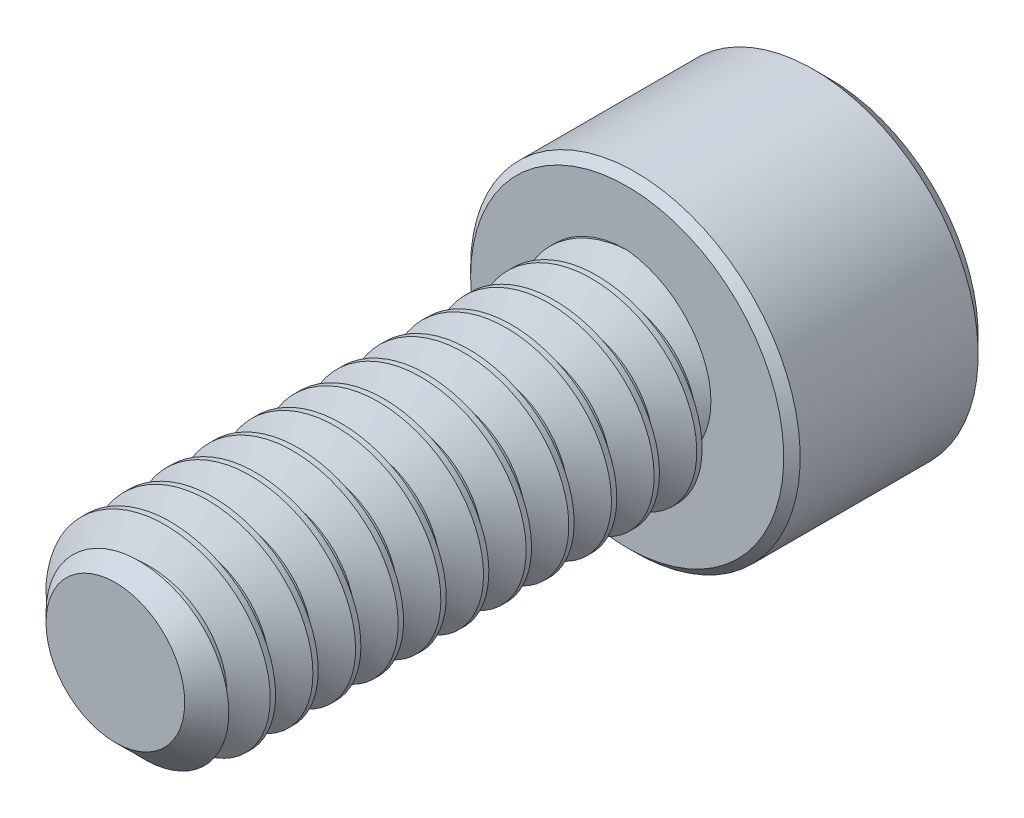
SolidWorks part; units mm, degrees
ref_plane "Front Plane" through (0, 0, 0) normal (0, 0, 1) x (1, 0, 0)
ref_plane "Top Plane" through (0, 0, 0) normal (0, 1, 0) x (1, 0, 0)
ref_plane "Right Plane" through (0, 0, 0) normal (1, 0, 0) x (0, 0, -1)
sketch "Sketch0" plane through (0, 0, 0) normal (1, 0, 0) x (0, 0, -1)
  line L0 (0, 0) -> (6.35, 0) construction
  point P2 (8.8646, 0)
  point P4 (0, 0)
  dimension "D1" = 6.35
  dimension "D2" = 2.5146
  dimension "Min Thread" = 0
sketch "Sketch1" plane through (0, 0, 0) normal (0, 0, 1) x (1, 0, 0)
  circle A0 centre (0, 0) radius 1.2573
  dimension "OD" = 2.5146
extrude "Extrude1" add sketch "Sketch1" against normal blind 6.35
sketch "Sketch2" plane through (0, 0, 0) normal (0, 0, 1) x (1, 0, 0)
  circle A0 centre (0, 0) radius 1.2573 construction
  circle A1 centre (0, 0) radius 1.2573
curve "Helix/Spiral1" pitch 0.5292 height 6.8792 radius 1.2573 centre (0, 0, 0) axis (0, 0, -1) start towards (0, 1, 0) parameters "pitch"=0.5292
chamfer "Chamfer3" distance 0.3969 angle 45 1 edges at (1.2573, 0, 0)
sketch "Sketch3" plane through (0, 0, 0) normal (1, 0, 0) x (0, 0, -1)
  line L0 (-0.463, 1.2573) -> (-0.2646, 0.9136)
  line L1 (-0.2646, 0.9136) -> (-0.1984, 0.9136)
  line L2 (-0.1984, 0.9136) -> (0, 1.2573)
  line L3 (-0.463, 1.2573) -> (0, 1.2573)
  line L4 (-0.2315, 1.2573) -> (-0.2315, 0.9136) construction
  line L5 (-0.3638, 1.0854) -> (-0.0992, 1.0854) construction
  line L6 (0, 1.2573) -> (0, -1.2573) construction
  dimension "D1" = 0.0661
  dimension "D2" = 0.2646
  dimension "D3" = 60
sweep "Cut-Sweep1" cut profiles "Sketch3" path "Helix/Spiral1" align with end faces yes
sketch "Sketch5" plane through (0, 0, 0) normal (1, 0, 0) x (0, 0, -1)
  line L0 (6.35, -0.9237) -> (6.35, 0.8971) construction
  line L1 (6.35, 1.2573) -> (0, 1.2573)
  line L2 (6.35, 1.2573) -> (6.35, 0)
  line L3 (6.35, 0) -> (-0.4576, 0)
  line L4 (0, 0) -> (6.35, 0) construction
  line L5 (0, 1.2573) -> (-0.4576, 0)
  line L6 (0, 0) -> (8.89, 0) construction
  dimension "D1" = 70
  dimension "D3" = 2.54
revolve "partially thread" [suppressed] add sketch "Sketch5" angle 360 about L6
sketch "Sketch6" plane through (0, 0, -6.35) normal (0, 0, -1) x (-1, 0, 0)
  circle A0 centre (0, 0) radius 2.0447
  dimension "head dia" = 4.0894
extrude "Extrude2" add sketch "Sketch6" along normal blind 2.5146
sketch "Sketch7" plane through (0, 0, -8.8646) normal (0, 0, -1) x (-1, 0, 0)
  line L1 (0, 1.1457) -> (-0.9922, 0.5728)
  line L2 (-0.9922, 0.5728) -> (-0.9922, -0.5728)
  line L3 (-0.9922, -0.5728) -> (0, -1.1457)
  line L4 (0, -1.1457) -> (0.9922, -0.5728)
  line L5 (0.9922, -0.5728) -> (0.9922, 0.5728)
  line L6 (0.9922, 0.5728) -> (0, 1.1457)
  circle A0 centre (0, 0) radius 0.9922 construction
  dimension "hex dia" = 1.9844
extrude "Cut-Extrude1" cut sketch "Sketch7" against normal blind 1.4883
sketch "Sketch8" plane through (0, 0, -8.8646) normal (0, 0, -1) x (-1, 0, 0)
  circle A0 centre (0, 0) radius 1.1457
extrude "Cut-Extrude2" cut sketch "Sketch8" against normal through all draft 45
chamfer "Chamfer1" distance 0.2045 angle 45 1 edges at (-2.0447, 0, -8.8646)
chamfer "Chamfer2" distance 0.1022 angle 45 1 edges at (-2.0447, 0, -6.35)
sketch "Sketch9" plane through (0, 0, 0) normal (1, 0, 0) x (0, 0, -1)
  line L0 (0, 1.2573) -> (0, -1.2573) construction
  line L1 (1.8521, 1.2573) -> (1.8521, -1.2573) construction
  line L2 (8.8646, 2.0447) -> (8.8646, -2.0447) construction
  line L3 (6.35, 2.0447) -> (6.35, -2.0447) construction
  line L4 (6.35, 1.9425) -> (6.35, -1.9425) construction
  line L5 (8.8646, -1.8402) -> (8.8646, 1.8402) construction
  line L6 (6.35, -2.0447) -> (6.35, 2.0447) construction
  line L7 (0, 0.8604) -> (0, -0.8604) construction
  line L8 (-0.463, 1.2573) -> (0, 1.2573) construction
  line L9 (1.8521, 0) -> (0, 0) construction
  dimension "D1" = 1.8521
equation "\"D3@Helix/Spiral1\" = \"screw length@Extrude1\"+\"pitch@Helix/Spiral1\""
equation "\"D1@Sketch3\" = \"pitch@Helix/Spiral1\"*.125"
equation "\"D2@Sketch3\" = \"pitch@Helix/Spiral1\"*.5"
equation "\"D1@Cut-Extrude1\" = \"hex dia@Sketch7\"*.75"
equation "\"D1@Chamfer1\" = \"head dia@Sketch6\"*.05"
equation "\"D1@Sketch9\" = \"pitch@Helix/Spiral1\"*3.50"
equation "\"D1@Chamfer2\" = \"D1@Chamfer1\"/2"
equation "\"D1@Chamfer3\" = \"pitch@Helix/Spiral1\"*.750"
equation "\"D1@Sketch0\" = \"screw length@Extrude1\""
equation "\"D2@Sketch0\" = \"head depth@Extrude2\""
